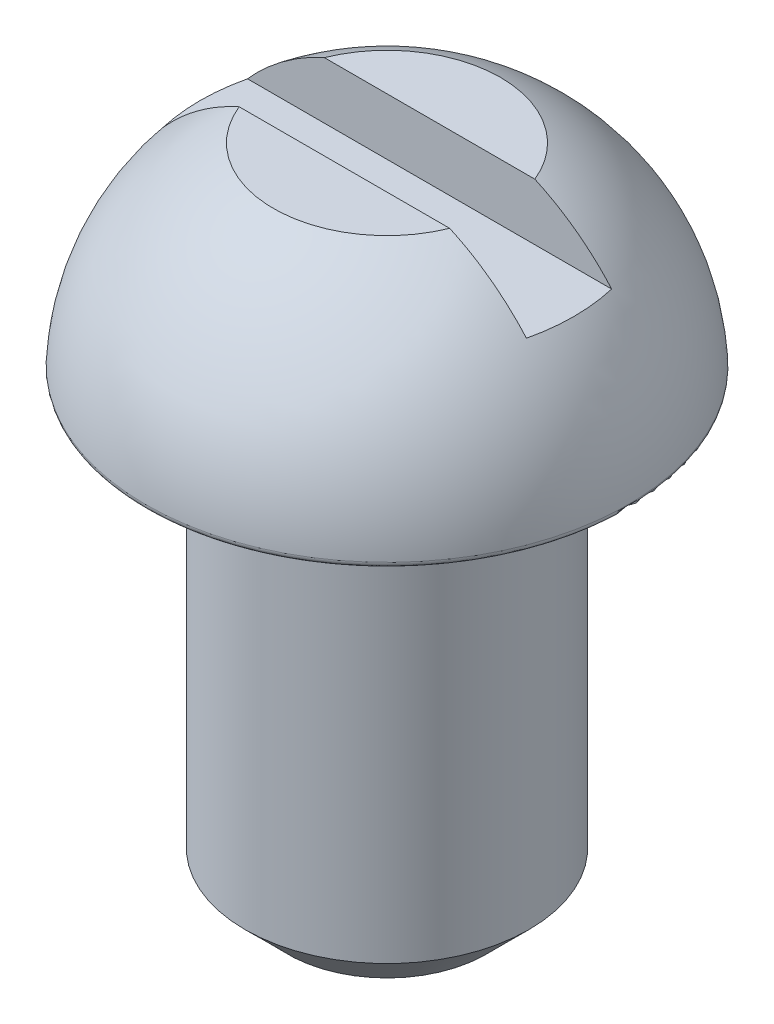
SolidWorks part; units mm, degrees
ref_plane "Спереди" through (0, 0, 0) normal (0, 0, 1) x (1, 0, 0)
ref_plane "Сверху" through (0, 0, 0) normal (0, 1, 0) x (1, 0, 0)
ref_plane "Справа" through (0, 0, 0) normal (1, 0, 0) x (0, 0, -1)
sketch "Эскиз1" plane through (0, 0, 0) normal (0, 0, 1) x (1, 0, 0)
  line L0 (4.25, 8) -> (2.5, 8)
  line L1 (0, 0) -> (0, 11.5)
  line L2 (2.5, 8) -> (2.5, 0.75)
  line L3 (2.5, 0.75) -> (1.75, 0)
  line L4 (1.75, 0) -> (0, 0)
  line L5 (0, 11.5) -> (2, 11.5)
  arc A0 (2, 11.5) -> (4.25, 8) centre (0.2512, 7.9025) cw
  point P9 (0, 0)
  dimension "D2" = 2
  dimension "D3" = 4
  dimension "D1" = 8
  dimension "D4" = 0.75
  dimension "D5" = 3.5
  dimension "D6" = 4.25
  dimension "D7" = 45
  dimension "D9" = 2.5
revolve "Повернуть1" add sketch "Эскиз1" angle 360 about L1
fillet "Скругление1" radius 0.1 1 edges at (0, 8, -4.25)
sketch "Эскиз3" plane through (0, 11.5, 0) normal (0, 1, 0) x (-1, 0, 0)
  line L1 (4, -0.75) -> (-4, -0.75)
  line L2 (4, -0.75) -> (4, 0.75)
  line L3 (4, 0.75) -> (-4, 0.75)
  line L4 (-4, -0.75) -> (-4, 0.75)
  dimension "D1" = 1.5
  dimension "D2" = 0.75
  dimension "D3" = 8
  dimension "D4" = 4
extrude "Вырез-Вытянуть2" cut sketch "Эскиз3" against normal blind 1
ref_axis "Ось1" through (0, -104.1565, 0) along (0, 1, 0)
